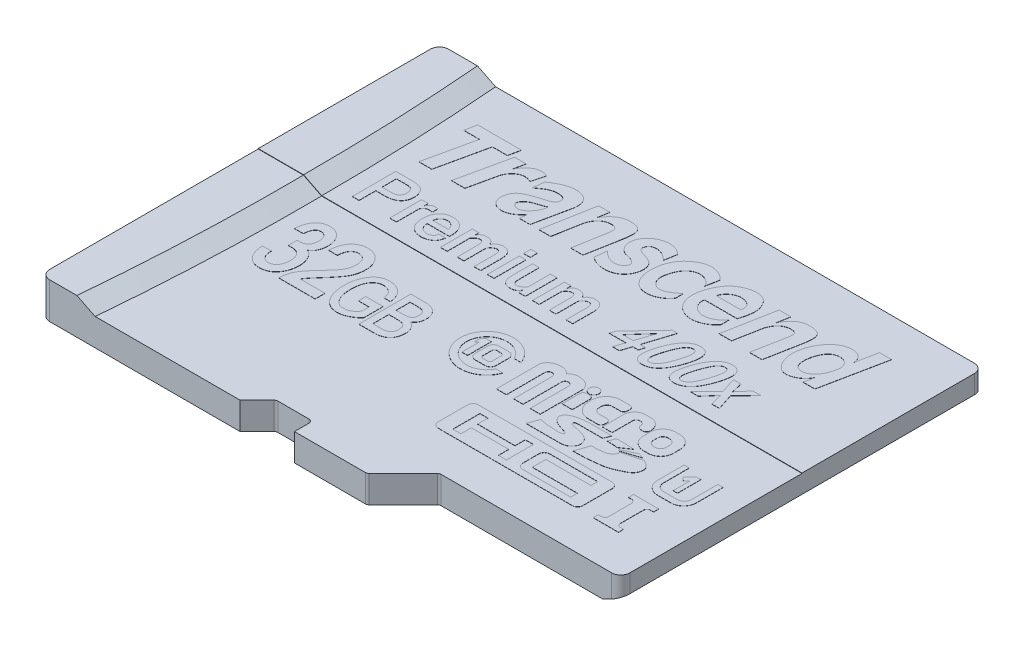
SolidWorks part; units mm, degrees
ref_plane "Front Plane" through (0, 0, 0) normal (0, 0, 1) x (1, 0, 0)
ref_plane "Top Plane" through (0, 0, 0) normal (0, 1, 0) x (1, 0, 0)
ref_plane "Right Plane" through (0, 0, 0) normal (1, 0, 0) x (0, 0, -1)
sketch "Sketch2" plane through (0, 0, 0) normal (0, 1, 0) x (1, 0, 0)
  line L0 (7.25, 5.5) -> (-7.25, 5.5)
  line L1 (-7.5, 5.25) -> (-7.5, -5.25)
  line L2 (-7.25, -5.5) -> (-2, -5.5)
  line L3 (-2, -5.5) -> (-1.5293, -5.0293)
  line L4 (-1.4586, -5) -> (-0.6, -5)
  line L5 (-0.5, -5.1) -> (-0.5, -5.5)
  line L8 (-0.5, -5.5) -> (1.4586, -5.5)
  line L9 (1.5293, -5.4707) -> (2.4707, -4.5293)
  line L10 (2.5414, -4.5) -> (7.25, -4.5)
  line L11 (7.5, -4.25) -> (7.5, 5.25)
  arc A0 (-1.4586, -5) -> (-1.5293, -5.0293) centre (-1.4586, -5.1) ccw
  arc A1 (-0.5, -5.1) -> (-0.6, -5) centre (-0.6, -5.1) ccw
  arc A3 (1.4586, -5.5) -> (1.5293, -5.4707) centre (1.4586, -5.4) ccw
  arc A4 (2.5414, -4.5) -> (2.4707, -4.5293) centre (2.5414, -4.6) ccw
  arc A5 (7.25, -4.5) -> (7.5, -4.25) centre (7.25, -4.25) ccw
  arc A6 (7.5, 5.25) -> (7.25, 5.5) centre (7.25, 5.25) ccw
  arc A7 (-7.5, -5.25) -> (-7.25, -5.5) centre (-7.25, -5.25) ccw
  arc A8 (-7.25, 5.5) -> (-7.5, 5.25) centre (-7.25, 5.25) ccw
  point P9 (-0.5, -5.5)
  point P10 (-0.5, -5.4707)
  point P26 (0, 0)
  point P28 (-7.5, -5.5)
  point P31 (-7.5, 5.5)
  dimension "D3" = 0.25
  dimension "D4" = 0.25
  dimension "D10" = 0.25
  dimension "D1" = 11
  dimension "D2" = 15
  dimension "D5" = 7.5
  dimension "D6" = 5.5
  dimension "D7" = 10
  dimension "D8" = 0.5
  dimension "D9" = 1
extrude "Boss-Extrude1" add sketch "Sketch2" along normal mid plane 1
sketch "Sketch4" plane through (0, 0, 0) normal (0, 0, 1) x (1, 0, 0)
  line L0 (-7.5, 0.5) -> (-6.25, 0.5)
  line L1 (-7.25, 0.5) -> (-2, 0.5) construction
  line L2 (-6.25, 0.5) -> (-5.75, 0.25)
  line L3 (-5.75, 0.25) -> (7.5, 0.25)
  line L4 (7.5, 0.5) -> (7.5, -0.5) construction
  line L5 (7.5, 0.25) -> (7.5, 1)
  line L6 (7.5, 1) -> (-7.5, 1)
  line L7 (-7.5, 1) -> (-7.5, 0.5)
  dimension "D1" = 0.75
  dimension "D2" = 0.75
  dimension "D3" = 1.25
  dimension "D4" = 0.5
extrude "Cut-Extrude1" cut sketch "Sketch4" against normal through all both and the other way through all
sketch "Sketch5" plane through (0, 0, 0) normal (0, 0, 1) x (1, 0, 0)
  line L1 (-4.75, 0.75) -> (-66.875, 0.75)
  line L2 (-66.875, 0.75) -> (-66.875, 0.5)
  line L4 (-7.5, 0.5) -> (-7.5, -0.5) construction
  line L5 (-66.875, 2.4541) -> (-66.875, -1.892) construction
  line L6 (-5.75, 0.25) -> (-6.25, 0.5)
  line L7 (-6.25, 0.5) -> (-66.875, 0.5)
  line L8 (-5.75, 0.25) -> (-4.75, 0.25)
  line L9 (-5.75, 0.25) -> (-2, 0.25) construction
  line L10 (-4.75, 0.25) -> (-4.75, 0.75)
  dimension "D1" = 0.5
  dimension "D2" = 59.375
  dimension "D3" = 1
revolve "Cut-Revolve1" cut sketch "Sketch5" angle 180 about L5 other way angle 0.5
ref_plane "Plane1" through (0, 0, -5.5) normal (0, 0, 1) x (1, 0, 0)
sketch "Sketch6" plane through (0, 0, -5.5) normal (0, 0, 1) x (1, 0, 0)
  line L0 (7.5, -0.5) -> (7.5, 0.26)
  line L2 (-7.5, 0.5) -> (-7.5, -0.5) construction
  line L4 (-7.5, -0.5) -> (-7.25, -0.5) construction
  line L5 (-7.5, -0.5) -> (7.5, -0.5)
  line L6 (-7.5, 0.51) -> (-5.5, 0.51)
  line L7 (-5.5, 0.51) -> (-5.5, 0.26)
  line L8 (-5.5, 0.26) -> (7.5, 0.26)
  line L9 (-7.5, 0.51) -> (-7.5, -0.5)
  dimension "D1" = 0.76
  dimension "D2" = 2
  dimension "D3" = 1.01
extrude "Boss-Extrude2" add sketch "Sketch6" along normal blind 5
ref_plane "Plane2" through (0, 0, -0.5) normal (0, 0, 1) x (1, 0, 0)
sketch "Sketch7" plane through (0, 0, -0.5) normal (0, 0, 1) x (1, 0, 0)
  line L0 (-6.2476, 0.51) -> (-5.7476, 0.26)
  line L2 (-6.2476, 0.51) -> (-67.5, 0.51)
  line L5 (7.5, 0.26) -> (-5.5, 0.26) construction
  line L6 (-5.75, 0.25) -> (-6.25, 0.5) construction
  line L7 (-5.7476, 0.26) -> (-5.2476, 0.26)
  line L8 (-5.2476, 0.26) -> (-5.2476, 0.76)
  line L9 (-5.2476, 0.76) -> (-67.5, 0.76)
  line L10 (-67.5, 0.76) -> (-67.5, 0.51)
  line L11 (-6.25, 0.5) -> (-6.5, 0.5) construction
  line L12 (-7.5, 0.5) -> (-7.5, -0.5) construction
  line L13 (-67.5, 1.5471) -> (-67.5, -0.1747) construction
  dimension "D1" = 0.01
  dimension "D2" = 0.01
  dimension "D3" = 0.5
  dimension "D4" = 0.5
  dimension "D5" = 60
revolve "Cut-Revolve2" cut sketch "Sketch7" angle 180 about L13 reverse direction yes
fillet "Fillet1" radius 0.25 2 edges at (-7.5, 0.005, -5.5) (7.5, -0.12, -5.5)
sketch "Sketch8" plane through (0, 0, 0) normal (0, 0, 1) x (1, 0, 0)
  line L0 (7.5, -0.25) -> (7, -0.5)
  line L1 (7.5, 0.25) -> (7.5, -0.5) construction
  line L2 (2.5414, -0.5) -> (7.25, -0.5) construction
  line L3 (7, -0.5) -> (7.5, -0.5)
  line L4 (7.5, -0.5) -> (7.5, -0.25)
  dimension "D1" = 0.25
  dimension "D2" = 0.5
extrude "Cut-Extrude2" cut sketch "Sketch8" against normal through all both and the other way through all
sketch "Sketch9" plane through (0, -0.5, 0) normal (0, -1, 0) x (1, 0, 0)
  line L0 (2.5414, 4.5) -> (7, 4.5) construction
  line L1 (6.5, 4) -> (3.5, 4)
  line L2 (6.5, 4) -> (6.5, 3.05)
  line L3 (6.5, 3.05) -> (3.5, 3.05)
  line L4 (3.5, 4) -> (3.5, 3.05)
  line L5 (6.5, 4) -> (3.5, 3.05) construction
  line L6 (6.5, 3.05) -> (3.5, 4) construction
  line L7 (6.5, 1.9) -> (3.5, 1.9)
  line L8 (6.5, 1.9) -> (6.5, 2.85)
  line L9 (6.5, 2.85) -> (3.5, 2.85)
  line L10 (3.5, 1.9) -> (3.5, 2.85)
  line L11 (6.5, 1.9) -> (3.5, 2.85) construction
  line L12 (6.5, 2.85) -> (3.5, 1.9) construction
  line L13 (6.5, 1.7) -> (3.5, 1.7)
  line L14 (6.5, 1.7) -> (6.5, 0.75)
  line L15 (6.5, 0.75) -> (3.5, 0.75)
  line L16 (3.5, 1.7) -> (3.5, 0.75)
  line L17 (6.5, 1.7) -> (3.5, 0.75) construction
  line L18 (6.5, 0.75) -> (3.5, 1.7) construction
  line L19 (6.5, -0.6) -> (3.5, -0.6)
  line L20 (6.5, -0.6) -> (6.5, -1.55)
  line L21 (6.5, -1.55) -> (3.5, -1.55)
  line L22 (3.5, -0.6) -> (3.5, -1.55)
  line L23 (6.5, -0.6) -> (3.5, -1.55) construction
  line L24 (6.5, -1.55) -> (3.5, -0.6) construction
  line L25 (6.75, -1.75) -> (3.5, -1.75)
  line L26 (6.75, -1.75) -> (6.75, -2.7)
  line L27 (6.75, -2.7) -> (3.5, -2.7)
  line L28 (3.5, -1.75) -> (3.5, -2.7)
  line L29 (6.75, -1.75) -> (3.5, -2.7) construction
  line L30 (6.75, -2.7) -> (3.5, -1.75) construction
  line L31 (3.5, -2.9) -> (6.5, -2.9)
  line L32 (3.5, -2.9) -> (3.5, -3.85)
  line L33 (3.5, -3.85) -> (6.5, -3.85)
  line L34 (6.5, -2.9) -> (6.5, -3.85)
  line L35 (3.5, -2.9) -> (6.5, -3.85) construction
  line L36 (3.5, -3.85) -> (6.5, -2.9) construction
  line L37 (6.5, -4.05) -> (3.5, -4.05)
  line L38 (6.5, -4.05) -> (6.5, -5)
  line L39 (6.5, -5) -> (3.5, -5)
  line L40 (3.5, -4.05) -> (3.5, -5)
  line L41 (6.5, -4.05) -> (3.5, -5) construction
  line L42 (6.5, -5) -> (3.5, -4.05) construction
  line L43 (6.75, 0.55) -> (3.5, 0.55)
  line L44 (6.75, 0.55) -> (6.75, -0.4)
  line L45 (6.75, -0.4) -> (3.5, -0.4)
  line L46 (3.5, 0.55) -> (3.5, -0.4)
  line L47 (6.75, 0.55) -> (3.5, -0.4) construction
  line L48 (6.75, -0.4) -> (3.5, 0.55) construction
  line L51 (7.5, -5.25) -> (7.5, 4.25) construction
  point P0 (5, 3.525)
  point P5 (5, 2.375)
  point P10 (5, 1.225)
  point P15 (5, -1.075)
  point P20 (5.125, -2.225)
  point P25 (5, -3.375)
  point P30 (5, -4.525)
  point P35 (5.125, 0.075)
  dimension "D1" = 0.95
  dimension "D2" = 0.2
  dimension "D3" = 0.2
  dimension "D4" = 0.2
  dimension "D5" = 0.2
  dimension "D6" = 0.2
  dimension "D7" = 0.2
  dimension "D8" = 0.2
  dimension "D9" = 0.5
  dimension "D10" = 4
  dimension "D11" = 3
  dimension "D12" = 3.25
extrude "Boss-Extrude3" add sketch "Sketch9" along normal blind 0.01
sketch "Sketch10" plane through (0, -0.5, 0) normal (0, -1, 0) x (1, 0, 0)
  line L0 (-1.4611, 4.2914) -> (-1.4611, -4.3118) construction
  line L1 (-7.5, -5.25) -> (-7.5, 5.25) construction
  text T0 "  C84931 4707" font "Microsoft Sans Serif" height in points 4
  point P4 (-1.4611, -4.9453)
  point P5 (-1.4611, 4.2914)
  point P6 (-1.502, -4.1074)
  point P8 (0, 0)
  point P9 (-1.4611, -4.3118)
  dimension "D1" = 6.0389
extrude "Boss-Extrude4" add sketch "Sketch10" along normal blind 0.01
sketch "Sketch11" plane through (0, -0.5, 0) normal (0, -1, 0) x (1, 0, 0)
  line L0 (-5.5, 4.7) -> (-5.5, -4.8286) construction
  line L1 (-7.5, -5.25) -> (-7.5, 5.25) construction
  line L3 (-7.25, 5.5) -> (-2, 5.5) construction
  text T0 "9181AA  32G  01DS2" font "Microsoft Sans Serif" height in points 3
  point P5 (-5.5, -4.8286)
  point P6 (-5.5, 4.6961)
  dimension "D1" = 2
  dimension "D2" = 0.8
extrude "Boss-Extrude5" add sketch "Sketch11" along normal blind 0.005
sketch "Sketch13" plane through (0, -0.5, 0) normal (0, -1, 0) x (1, 0, 0)
  line L0 (-6.75, 4.7) -> (-6.75, -4.9658) construction
  line L1 (-7.25, 5.5) -> (-2, 5.5) construction
  line L3 (-7.5, -5.25) -> (-7.5, 5.25) construction
  text T0 "Made  In  Taiwan" font "Microsoft Sans Serif" height in points 3
  dimension "D1" = 0.8
  dimension "D2" = 0.75
extrude "Boss-Extrude6" add sketch "Sketch13" along normal blind 0.005
sketch "Sketch15" plane through (0, 0.26, 0) normal (0, 1, 0) x (1, 0, 0)
  line L0 (158.8303, 491.6959) -> (825.497, 491.6959) construction
  line L1 (-5.2862, 4.338) -> (-5.3422, 4.0172)
  line L2 (-5.3422, 4.0172) -> (-4.9144, 4.0172)
  line L3 (-4.9144, 4.0172) -> (-5.2149, 2.6473)
  line L4 (-5.2149, 2.6473) -> (-4.8584, 2.6473)
  line L5 (-4.8584, 2.6473) -> (-4.5579, 4.0172)
  line L6 (-4.5579, 4.0172) -> (-4.1455, 4.0172)
  line L7 (-4.1455, 4.0172) -> (-4.0751, 4.338)
  line L8 (-4.0751, 4.338) -> (-5.2862, 4.338)
  line L9 (-4.0029, 4.0732) -> (-4.3156, 2.6473)
  line L10 (-4.3156, 2.6473) -> (-3.9474, 2.6473)
  line L11 (-3.9474, 2.6473) -> (-3.7739, 3.4383)
  line L12 (-4.0029, 4.0732) -> (-3.6821, 4.0732)
  line L13 (-3.6821, 4.0732) -> (-3.7527, 3.7511)
  line L14 (-3.1168, 4.0732) -> (-3.2136, 3.7014)
  line L15 (-2.9924, 3.8987) -> (-3.0268, 3.5897)
  line L16 (-2.4525, 2.8946) -> (-2.48, 2.6814)
  line L17 (-2.48, 2.6814) -> (-2.1843, 2.6814)
  line L18 (-2.1843, 2.6814) -> (-1.9711, 3.7014)
  line L21 (-1.9361, 2.6814) -> (-1.6843, 4.0732)
  line L22 (-1.6843, 4.0732) -> (-1.3721, 4.0732)
  line L23 (-1.3721, 4.0732) -> (-1.4304, 3.7511)
  line L24 (-1.9361, 2.6814) -> (-1.6138, 2.6814)
  line L25 (-1.6138, 2.6814) -> (-1.4715, 3.468)
  line L26 (-0.8988, 3.5897) -> (-1.0631, 2.6814)
  line L27 (-1.0631, 2.6814) -> (-0.7243, 2.6814)
  line L28 (-0.7243, 2.6814) -> (-0.5397, 3.7014)
  line L29 (0.5669, 3.9963) -> (0.5114, 3.662)
  line L30 (-0.4808, 3.1215) -> (-0.52, 2.7788)
  line L31 (1.7649, 3.9712) -> (1.6987, 3.6155)
  line L32 (1.5815, 3.1416) -> (1.5815, 2.9253)
  line L33 (2.0827, 3.5483) -> (2.7624, 3.5483)
  line L34 (2.0249, 3.288) -> (2.9251, 3.288)
  line L35 (2.8419, 3.1416) -> (2.8419, 2.9253)
  line L36 (3.0337, 2.6814) -> (3.2951, 4.0714)
  line L37 (3.2951, 4.0714) -> (3.6224, 4.0714)
  line L38 (3.6224, 4.0714) -> (3.5565, 3.7213)
  line L39 (3.0337, 2.6814) -> (3.3731, 2.6814)
  line L40 (3.3731, 2.6814) -> (3.5154, 3.4382)
  line L41 (4.0687, 3.5636) -> (3.8974, 2.6528)
  line L42 (3.8974, 2.6528) -> (4.2442, 2.6528)
  line L43 (4.2442, 2.6528) -> (4.4362, 3.6737)
  line L44 (5.6976, 4.4384) -> (6.0299, 4.4384)
  line L45 (6.0299, 4.4384) -> (5.6739, 2.6814)
  line L46 (5.6739, 2.6814) -> (5.3484, 2.6814)
  line L47 (5.3484, 2.6814) -> (5.4066, 2.9686)
  line L48 (5.6976, 4.4384) -> (5.5783, 3.8494)
  line L49 (-2.359, 3.2688) -> (-2.3486, 3.354)
  spline S0 degree 3 poles (-3.7527, 3.7511) (-3.6407, 3.9755) (-3.4147, 4.1987) (-3.1168, 4.0732) knots 0 0 0 0 1 1 1 1
  spline S1 degree 3 poles (-3.7739, 3.4383) (-3.707, 3.6572) (-3.469, 3.854) (-3.2136, 3.7014) knots 0 0 0 0 1 1 1 1
  spline S2 degree 3 poles (-2.9924, 3.8987) (-2.8373, 4.0051) (-2.4473, 4.234) (-1.9267, 4.089) (-1.9711, 3.7014) knots 0 0 0 0 0.427464 1 1 1 1
  spline S3 degree 3 poles (-3.0268, 3.5897) (-2.9262, 3.6662) (-2.7469, 3.8047) (-2.4945, 3.8221) (-2.3204, 3.7633) (-2.3195, 3.5384) (-2.6092, 3.4705) (-2.8655, 3.3808) (-3.1477, 3.263) (-3.2689, 2.9868) (-3.1997, 2.6846) (-2.8048, 2.5588) (-2.5561, 2.7501) (-2.4525, 2.8946) knots 0 0 0 0 0.125339 0.201806 0.242081 0.279775 0.378143 0.472332 0.560271 0.655256 0.737774 0.82471 1 1 1 1
  spline S4 degree 3 poles (-2.3486, 3.354) (-2.5064, 3.2611) (-2.7369, 3.2767) (-2.9384, 2.9914) (-2.6347, 2.7517) (-2.3775, 3.1441) (-2.359, 3.2688) knots 0 0 0 0 0.359916 0.478899 0.575608 1 1 1 1
  spline S5 degree 3 poles (-1.4304, 3.7511) (-1.3229, 3.9458) (-1.0782, 4.186) (-0.5312, 4.103) (-0.5169, 3.9068) (-0.5397, 3.7014) knots 0 0 0 0 0.477961 0.720245 1 1 1 1
  spline S6 degree 3 poles (-1.4715, 3.468) (-1.4275, 3.6194) (-1.2734, 3.8305) (-0.9177, 3.8046) (-0.8856, 3.7054) (-0.8988, 3.5897) knots 0 0 0 0 0.54471 0.774016 1 1 1 1
  spline S7 degree 3 poles (0.5669, 3.9963) (0.4245, 4.1604) (0.0713, 4.1878) (-0.3085, 3.9466) (-0.45, 3.5885) (-0.2437, 3.2852) (-0.0068, 3.2776) (0.2118, 3.1384) (-0.0449, 2.8001) (-0.3756, 2.9847) (-0.4808, 3.1215) knots 0 0 0 0 0.21526 0.330731 0.465297 0.578093 0.652065 0.72378 0.787706 1 1 1 1
  spline S8 degree 3 poles (-0.52, 2.7788) (-0.3271, 2.6259) (0.1314, 2.5732) (0.4603, 2.9649) (0.484, 3.3777) (0.1857, 3.5186) (-0.1102, 3.583) (-0.0426, 3.8241) (0.2373, 3.885) (0.4177, 3.7609) (0.5114, 3.662) knots 0 0 0 0 0.273899 0.389369 0.52759 0.637897 0.730225 0.781048 0.851979 1 1 1 1
  spline S9 degree 3 poles (1.6987, 3.6155) (1.6353, 3.7933) (1.2773, 3.925) (0.9827, 3.6447) (0.8803, 3.3712) (0.8613, 3.0739) (1.1849, 2.8102) (1.4705, 3.0525) (1.5815, 3.1416) knots 0 0 0 0 0.249144 0.382676 0.50918 0.650083 0.751503 1 1 1 1
  spline S10 degree 3 poles (1.5815, 2.9253) (1.4692, 2.7716) (1.1993, 2.6072) (0.7921, 2.6749) (0.579, 2.9508) (0.5474, 3.3325) (0.6378, 3.7423) (0.9132, 4.0416) (1.3205, 4.2365) (1.6462, 4.1211) (1.7649, 3.9712) knots 0 0 0 0 0.175141 0.260201 0.354064 0.468722 0.602099 0.725908 0.827802 1 1 1 1
  spline S11 degree 3 poles (2.9251, 3.288) (2.9845, 3.4777) (3.0667, 3.8058) (2.7712, 4.2244) (2.3523, 4.1734) (1.9835, 3.9584) (1.7665, 3.5529) (1.701, 3.0955) (1.9113, 2.7446) (2.3511, 2.5665) (2.7078, 2.7438) (2.8419, 2.9253) knots 0 0 0 0 0.153735 0.227091 0.34284 0.421144 0.543478 0.670248 0.746283 0.830069 1 1 1 1
  spline S12 degree 3 poles (2.0249, 3.288) (1.9797, 3.0931) (2.3276, 2.7379) (2.7286, 2.9979) (2.8419, 3.1416) knots 0 0 0 0 0.473851 1 1 1 1
  spline S13 degree 3 poles (2.0827, 3.5483) (2.1348, 3.7177) (2.4404, 3.9586) (2.8155, 3.7601) (2.7624, 3.5483) knots 0 0 0 0 0.518429 1 1 1 1
  spline S14 degree 3 poles (3.5565, 3.7213) (3.6506, 3.9205) (3.8841, 4.173) (4.4549, 4.0813) (4.4586, 3.8752) (4.4362, 3.6737) knots 0 0 0 0 0.455916 0.725539 1 1 1 1
  spline S15 degree 3 poles (3.5154, 3.4382) (3.5628, 3.5902) (3.7063, 3.7994) (4.0752, 3.7768) (4.0815, 3.6758) (4.0687, 3.5636) knots 0 0 0 0 0.549476 0.780788 1 1 1 1
  spline S16 degree 3 poles (5.5783, 3.8494) (5.5592, 4.1376) (5.1279, 4.2091) (4.7223, 3.8887) (4.5013, 3.4516) (4.4939, 2.9566) (4.8844, 2.4839) (5.3323, 2.7662) (5.4066, 2.9686) knots 0 0 0 0 0.207472 0.326046 0.481805 0.666148 0.774125 1 1 1 1
  spline S17 degree 3 poles (5.4203, 3.1268) (5.5117, 3.3885) (5.5486, 3.6091) (5.3809, 3.8102) (5.0554, 3.7984) (4.8954, 3.5148) (4.8358, 3.2482) (4.8567, 2.9415) (5.216, 2.8879) (5.4203, 3.1268) (5.5117, 3.3885) (5.5486, 3.6091) knots -0.338143 -0.248717 -0.08126 0 0.107798 0.173296 0.302086 0.439095 0.539418 0.661857 0.751283 0.91874 1 1.107798 1.173296 1.302086 only from (5.501, 3.3736) to (5.501, 3.3736)
  point P157 (-2.3408, 3.7437)
  point P161 (-2.333, 3.626)
extrude "Boss-Extrude7" add sketch "Sketch15" along normal blind 0.005
sketch "Sketch17" plane through (0, 0.26, 0) normal (0, 1, 0) x (1, 0, 0)
  line L0 (-5.4255, 0.9) -> (0.8836, 0.9) construction
  line L1 (7.5, 0.5) -> (-5.7476, 0.5) construction
  text T0 "Premium" font "Microsoft Sans Serif" height 1.2
  point P5 (-5.5165, 0.9)
  point P6 (-5.4255, 0.9)
  dimension "D1" = 0.4
extrude "Boss-Extrude8" add sketch "Sketch17" along normal blind 0.005
sketch "Sketch18" plane through (0, 0.26, 0) normal (0, 1, 0) x (1, 0, 0)
  line L0 (1.3851, 0.9) -> (5.1819, 0.9) construction
  line L1 (7.5, 0.5) -> (-5.7476, 0.5) construction
  text T0 "400x" font "Microsoft Sans Serif" height 1.2
  dimension "D1" = 0.4
extrude "Boss-Extrude9" add sketch "Sketch18" along normal blind 0.005
sketch "Sketch19" plane through (0, 0.25, 0) normal (0, 1, 0) x (1, 0, 0)
  line L0 (-5.4698, -2.05) -> (-1.0866, -2.05) construction
  line L1 (-5.9979, -5.5) -> (-2, -5.5) construction
  text T0 "32" font "Microsoft Sans Serif" height in points 8
  dimension "D1" = 3.45
extrude "Boss-Extrude10" add sketch "Sketch19" along normal blind 0.005
sketch "Sketch20" plane through (0, 0.25, 0) normal (0, 1, 0) x (1, 0, 0)
  line L0 (-3.774, -2.05) -> (-0.8585, -2.05) construction
  line L1 (-3.3771, -2.05) -> (-4.3818, -2.05) construction
  line L2 (-3.3771, -2.05) -> (-4.3818, -2.05) construction
  text T0 "GB" font "Microsoft Sans Serif" height in points 6
  point P6 (-0.8585, -2.05)
  point P7 (-3.3771, -2.05)
  point P10 (-3.5784, -2.05)
  point P11 (-3.774, -2.05)
extrude "Boss-Extrude11" add sketch "Sketch20" along normal blind 0.005
sketch "Sketch21" plane through (0, 0.255, 0) normal (0, 1, 0) x (1, 0, 0)
  line L0 (-2.259, -1.2965) -> (-2.259, -2.05) construction
  line L1 (-2.259, -1.2965) -> (-2.259, -2.05) construction
  line L2 (-2.259, -1.8294) -> (-2.259, -1.6982)
  line L3 (-2.259, -1.6982) -> (-2.622, -1.9356)
  line L4 (-2.622, -1.9356) -> (-2.5746, -2.0367)
  spline S0 degree 2 poles (-2.5746, -2.0367) (-2.3903, -1.9703) (-2.259, -1.8294) knots 0 0 0 1 1 1
  spline S2 degree 3 poles (-2.4284, -1.9035) (-2.4355, -1.9168) (-2.4495, -1.9429) (-2.4789, -1.9765) (-2.513, -2.0054) (-2.5532, -2.0285) (-2.5987, -2.0466) (-2.6499, -2.0593) (-2.7066, -2.0671) (-2.7463, -2.0679) (-2.767, -2.0684) knots 0 0 0 0 0.112738 0.222655 0.333672 0.448018 0.569947 0.70158 0.844182 1 1 1 1 construction
extrude "Boss-Extrude12" add sketch "Sketch21" against normal blind 0.005
sketch "Sketch22" plane through (0, 0.25, 0) normal (0, 1, 0) x (1, 0, 0)
  line L0 (-2.259, -1.8294) -> (-2.259, -2.0681)
  line L1 (-2.259, -2.0681) -> (-2.5746, -2.0681)
  line L2 (-2.5746, -2.0681) -> (-2.5746, -2.0367)
  parabola Q0 (-2.5746, -2.0367) -> (-2.259, -1.8294) focus (-2.6055, -1.6185) apex (-2.3801, -1.9356) construction
  parabola Q1 (-2.5746, -2.0367) -> (-2.259, -1.8294) focus (-2.6055, -1.6185) apex (-2.3801, -1.9356)
extrude "Cut-Extrude4" cut sketch "Sketch22" along normal blind 0.005
sketch "Sketch23" plane through (0, 0.25, 0) normal (0, 1, 0) x (1, 0, 0)
  line L0 (0.787, -0.7291) -> (0.9803, -0.7291)
  line L1 (0.787, -1.2312) -> (0.9803, -1.2312)
  line L2 (-0.0838, -1.2966) -> (0.0714, -1.2966)
  line L3 (0.0714, -1.2966) -> (0.0714, -0.641)
  line L4 (0.0714, -0.641) -> (-0.0838, -0.641)
  line L5 (-0.0838, -0.641) -> (-0.1581, -0.7152)
  line L6 (-0.1581, -0.7152) -> (-0.1581, -0.8857)
  line L7 (-0.1581, -0.8857) -> (-0.0838, -0.8114)
  line L8 (-0.0838, -0.8114) -> (-0.0838, -1.2966)
  line L9 (1.2708, -1.6991) -> (1.5458, -1.6991)
  line L10 (0.3492, -0.7776) -> (0.4882, -0.7776)
  line L11 (0.2892, -0.8376) -> (0.2892, -1.0992)
  line L12 (0.3492, -1.1592) -> (0.4882, -1.1592)
  line L13 (0.5482, -0.8376) -> (0.5482, -1.0992)
  line L14 (0.2892, -0.7776) -> (0.5482, -1.1592) construction
  line L15 (0.2892, -1.1592) -> (0.5482, -0.7776) construction
  line L16 (0.2799, -0.6402) -> (0.5575, -0.6402)
  line L17 (0.1299, -0.7902) -> (0.1299, -1.1466)
  line L18 (0.2799, -1.2966) -> (0.5575, -1.2966)
  line L19 (0.7075, -0.7902) -> (0.7075, -1.1466)
  line L20 (0.1299, -0.6402) -> (0.7075, -1.2966) construction
  line L21 (0.1299, -1.2966) -> (0.7075, -0.6402) construction
  line L22 (1.5458, -1.6991) -> (1.5458, -0.6402)
  line L23 (1.2708, -1.6991) -> (1.2708, -0.5012)
  line L24 (1.8741, -0.2054) -> (1.8741, -1.7553) construction
  line L25 (1.7436, -1.6991) -> (1.7436, -0.6402)
  line L26 (2.0045, -1.6991) -> (2.0045, -0.6402)
  line L27 (2.4774, -1.6991) -> (2.4774, -0.5012)
  line L28 (2.2023, -1.6991) -> (2.2023, -0.6402)
  line L29 (2.4774, -1.6991) -> (2.2023, -1.6991)
  line L30 (1.7436, -1.6991) -> (2.0045, -1.6991)
  line L31 (2.5303, -1.1466) -> (2.8095, -1.1466)
  line L32 (2.5303, -1.1466) -> (2.5303, -0.6637)
  line L33 (2.6303, -0.5637) -> (2.7095, -0.5637)
  line L34 (2.8095, -0.6637) -> (2.8095, -1.1466)
  line L35 (3.6027, -0.9857) -> (3.6027, -1.0466)
  line L36 (3.2863, -0.5185) -> (3.5027, -0.5185)
  line L37 (3.1363, -0.6685) -> (3.1363, -0.7357)
  line L38 (3.2863, -0.8857) -> (3.5027, -0.8857)
  line L40 (3.1363, -0.5185) -> (3.6027, -0.8857) construction
  line L41 (3.1363, -0.8857) -> (3.6027, -0.5185) construction
  line L42 (3.2499, -0.2504) -> (3.5027, -0.2504)
  line L43 (2.8499, -0.6504) -> (2.8499, -0.7466)
  line L44 (3.2499, -1.1466) -> (3.5027, -1.1466)
  line L45 (3.6027, -0.3504) -> (3.6027, -0.4185)
  line L46 (2.8499, -0.2504) -> (3.6027, -1.1466) construction
  line L47 (2.8499, -1.1466) -> (3.6027, -0.2504) construction
  line L48 (3.6375, -0.5614) -> (3.6375, -1.1466)
  line L49 (3.6375, -1.1466) -> (3.9091, -1.1466)
  line L50 (3.9091, -1.1466) -> (3.9091, -0.583)
  line L51 (3.9375, -0.2614) -> (4.0935, -0.2614)
  line L52 (4.3934, -0.5685) -> (4.393, -0.5863)
  line L53 (4.293, -0.684) -> (4.2369, -0.684)
  line L54 (4.1369, -0.584) -> (4.1369, -0.583)
  line L55 (4.0369, -0.483) -> (4.0091, -0.483)
  line L56 (3.9874, -1.2312) -> (3.9114, -1.4138)
  line L57 (4.8124, -0.5012) -> (4.8584, -0.5012)
  line L58 (4.6624, -0.6512) -> (4.6624, -0.7576)
  line L59 (4.8124, -0.9076) -> (4.8584, -0.9076)
  line L60 (5.0084, -0.6512) -> (5.0084, -0.7576)
  line L61 (4.6624, -0.5012) -> (5.0084, -0.9076) construction
  line L62 (4.6624, -0.9076) -> (5.0084, -0.5012) construction
  line L63 (4.772, -0.2621) -> (4.8988, -0.2621)
  line L64 (4.422, -0.6121) -> (4.422, -0.7966)
  line L65 (4.772, -1.1466) -> (4.8988, -1.1466)
  line L66 (5.2488, -0.6121) -> (5.2488, -0.7966)
  line L67 (4.422, -0.2621) -> (5.2488, -1.1466) construction
  line L68 (4.422, -1.1466) -> (5.2488, -0.2621) construction
  line L69 (2.505, -2.1156) -> (2.6129, -1.8203)
  line L70 (2.505, -2.1156) -> (3.4415, -2.1156)
  line L71 (3.9114, -1.4138) -> (3.2148, -1.4138)
  line L72 (3.9874, -1.2312) -> (3.4062, -1.2312)
  line L73 (4.122, -1.2312) -> (4.0444, -1.4177)
  line L74 (3.9375, -1.7553) -> (3.8087, -2.1274)
  line L75 (4.4769, -1.5186) -> (5.018, -1.3725)
  line L76 (4.4497, -1.4902) -> (4.9316, -1.332)
  line L77 (4.4067, -1.462) -> (4.7897, -1.2837)
  line L78 (4.3329, -1.4362) -> (4.6022, -1.2496)
  line L79 (6.6072, -0.9287) -> (6.75, -0.9287)
  line L80 (5.6764, -0.9287) -> (5.8194, -0.9287)
  line L81 (5.6764, -0.9287) -> (5.6764, -1.6659)
  line L82 (6.0264, -2.0159) -> (6.4, -2.0159)
  line L83 (6.75, -0.9287) -> (6.75, -1.6659)
  line L84 (5.6764, -0.9287) -> (6.75, -2.0159) construction
  line L85 (5.6764, -2.0159) -> (6.75, -0.9287) construction
  line L86 (6.0194, -1.8497) -> (6.4072, -1.8497)
  line L87 (5.8194, -1.6497) -> (5.8194, -0.9287)
  line L89 (6.6072, -1.6497) -> (6.6072, -0.9287)
  line L90 (5.8194, -1.8497) -> (6.6072, -0.9287) construction
  line L91 (5.8194, -0.9287) -> (6.6072, -1.8497) construction
  line L92 (6.035, -1.3242) -> (5.9483, -1.2364)
  line L93 (5.9483, -1.2364) -> (6.1405, -1.0466)
  line L94 (6.1405, -1.0466) -> (6.2572, -1.0466)
  line L95 (6.2572, -1.0466) -> (6.2572, -1.6912)
  line L96 (6.2572, -1.6912) -> (6.1387, -1.6912)
  line L97 (6.1387, -1.6912) -> (6.1387, -1.2292)
  line L98 (6.1387, -1.2292) -> (6.035, -1.3242)
  line L99 (5.1746, -3.4199) -> (5.2488, -3.4405) construction
  line L100 (1.4043, -2.3311) -> (5.0988, -2.3311)
  line L101 (1.2543, -2.4811) -> (1.2543, -3.2905)
  line L102 (1.4043, -3.4405) -> (5.0988, -3.4405)
  line L103 (5.2488, -2.4811) -> (5.2488, -3.2905)
  line L104 (1.2543, -2.3311) -> (1.3284, -2.3517) construction
  line L105 (1.2543, -3.4405) -> (1.3284, -3.4199) construction
  line L106 (5.1746, -2.3517) -> (5.2488, -2.3311) construction
  line L107 (1.6307, -2.5164) -> (1.8534, -2.5164)
  line L108 (1.8534, -2.5164) -> (1.8534, -2.8001)
  line L109 (1.8534, -2.8001) -> (2.8839, -2.8001)
  line L110 (2.8839, -2.8001) -> (2.8839, -2.5164)
  line L111 (2.8839, -2.5164) -> (3.1067, -2.5164)
  line L112 (3.1067, -2.5164) -> (3.1067, -3.2614)
  line L113 (3.1067, -3.2614) -> (2.8839, -3.2614)
  line L114 (2.8839, -3.2614) -> (2.8839, -2.9738)
  line L115 (2.8839, -2.9738) -> (1.8534, -2.9738)
  line L116 (1.8534, -2.9738) -> (1.8534, -3.2614)
  line L117 (1.8534, -3.2614) -> (1.6307, -3.2614)
  line L118 (1.6307, -3.2614) -> (1.6307, -2.5164)
  line L119 (4.8823, -2.5164) -> (4.8823, -2.7029)
  line L120 (4.8823, -2.7029) -> (3.6375, -2.7029)
  line L121 (3.6375, -2.7029) -> (3.6375, -3.0748)
  line L122 (3.6375, -3.0748) -> (4.8823, -3.0748)
  line L123 (4.8823, -3.0748) -> (4.8823, -3.2614)
  line L124 (4.8823, -3.2614) -> (3.5562, -3.2614)
  line L125 (3.4062, -3.1114) -> (3.4062, -2.6664)
  line L126 (3.5562, -2.5164) -> (4.8823, -2.5164)
  line L127 (5.6838, -2.4709) -> (5.8684, -2.4709)
  line L129 (5.6838, -2.4709) -> (5.6838, -2.3311)
  line L130 (5.6838, -2.3311) -> (6.3775, -2.3311)
  line L131 (6.3775, -2.4709) -> (6.3775, -2.3311)
  line L132 (5.6838, -3.4405) -> (6.3775, -2.3311) construction
  line L133 (5.6838, -2.3311) -> (6.3775, -3.4405) construction
  line L134 (5.8684, -2.4709) -> (5.8684, -3.3007)
  line L135 (6.3775, -2.4709) -> (6.1929, -2.4709)
  line L136 (6.1929, -2.4709) -> (6.1929, -3.3007)
  line L137 (5.9483, -2.8858) -> (6.1245, -2.8858) construction
  line L138 (5.6838, -3.3007) -> (5.8684, -3.3007)
  line L139 (5.6838, -3.3007) -> (5.6838, -3.4405)
  line L140 (5.6838, -3.4405) -> (6.3775, -3.4405)
  line L141 (6.3775, -3.3007) -> (6.3775, -3.4405)
  line L142 (6.3775, -3.3007) -> (6.1929, -3.3007)
  arc A0 (0.9803, -0.7291) -> (0.9803, -1.2312) centre (0.2866, -0.9801) ccw
  arc A1 (0.787, -0.7291) -> (0.787, -1.2312) centre (0.2866, -0.9801) ccw
  arc A2 (0.4882, -1.1592) -> (0.5482, -1.0992) centre (0.4882, -1.0992) ccw
  arc A3 (0.2892, -1.0992) -> (0.3492, -1.1592) centre (0.3492, -1.0992) ccw
  arc A4 (0.3492, -0.7776) -> (0.2892, -0.8376) centre (0.3492, -0.8376) ccw
  arc A5 (0.4882, -0.7776) -> (0.5482, -0.8376) centre (0.4882, -0.8376) cw
  arc A6 (0.5575, -1.2966) -> (0.7075, -1.1466) centre (0.5575, -1.1466) ccw
  arc A7 (0.1299, -1.1466) -> (0.2799, -1.2966) centre (0.2799, -1.1466) ccw
  arc A8 (0.2799, -0.6402) -> (0.1299, -0.7902) centre (0.2799, -0.7902) ccw
  arc A9 (0.5575, -0.6402) -> (0.7075, -0.7902) centre (0.5575, -0.7902) cw
  arc A11 (1.7436, -0.6402) -> (1.5458, -0.6402) centre (1.6447, -0.6402) ccw
  arc A12 (2.0045, -0.6402) -> (2.2023, -0.6402) centre (2.1034, -0.6402) cw
  circle A13 centre (2.6659, -0.4029) radius 0.135
  arc A15 (2.5303, -0.6637) -> (2.6303, -0.5637) centre (2.6303, -0.6637) cw
  arc A16 (2.8095, -0.6637) -> (2.7095, -0.5637) centre (2.7095, -0.6637) ccw
  arc A17 (3.5027, -1.1466) -> (3.6027, -1.0466) centre (3.5027, -1.0466) ccw
  arc A18 (3.5027, -0.8857) -> (3.6027, -0.9857) centre (3.5027, -0.9857) cw
  arc A19 (3.5027, -0.5185) -> (3.6027, -0.4185) centre (3.5027, -0.4185) ccw
  arc A20 (3.5027, -0.2504) -> (3.6027, -0.3504) centre (3.5027, -0.3504) cw
  arc A21 (3.2863, -0.5185) -> (3.1363, -0.6685) centre (3.2863, -0.6685) ccw
  arc A22 (3.1363, -0.7357) -> (3.2863, -0.8857) centre (3.2863, -0.7357) ccw
  arc A23 (2.8499, -0.7466) -> (3.2499, -1.1466) centre (3.2499, -0.7466) ccw
  arc A24 (3.2499, -0.2504) -> (2.8499, -0.6504) centre (3.2499, -0.6504) ccw
  arc A25 (4.1369, -0.583) -> (4.0369, -0.483) centre (4.0369, -0.583) ccw
  arc A26 (3.9091, -0.583) -> (4.0091, -0.483) centre (4.0091, -0.583) cw
  arc A27 (4.393, -0.5863) -> (4.293, -0.684) centre (4.293, -0.584) cw
  arc A28 (4.1369, -0.584) -> (4.2369, -0.684) centre (4.2369, -0.584) ccw
  arc A29 (4.0935, -0.2614) -> (4.3934, -0.5685) centre (4.0935, -0.5614) cw
  arc A30 (3.6375, -0.5614) -> (3.9375, -0.2614) centre (3.9375, -0.5614) cw
  arc A31 (4.8988, -1.1466) -> (5.2488, -0.7966) centre (4.8988, -0.7966) ccw
  arc A32 (4.422, -0.7966) -> (4.772, -1.1466) centre (4.772, -0.7966) ccw
  arc A33 (4.772, -0.2621) -> (4.422, -0.6121) centre (4.772, -0.6121) ccw
  arc A34 (4.8988, -0.2621) -> (5.2488, -0.6121) centre (4.8988, -0.6121) cw
  arc A35 (4.8584, -0.9076) -> (5.0084, -0.7576) centre (4.8584, -0.7576) ccw
  arc A36 (4.6624, -0.7576) -> (4.8124, -0.9076) centre (4.8124, -0.7576) ccw
  arc A37 (4.8124, -0.5012) -> (4.6624, -0.6512) centre (4.8124, -0.6512) ccw
  arc A38 (4.8584, -0.5012) -> (5.0084, -0.6512) centre (4.8584, -0.6512) cw
  arc A39 (6.4072, -1.8497) -> (6.6072, -1.6497) centre (6.4072, -1.6497) ccw
  arc A40 (6.0194, -1.8497) -> (5.8194, -1.6497) centre (6.0194, -1.6497) cw
  arc A41 (6.4, -2.0159) -> (6.75, -1.6659) centre (6.4, -1.6659) ccw
  arc A42 (5.6764, -1.6659) -> (6.0264, -2.0159) centre (6.0264, -1.6659) ccw
  arc A43 (5.0988, -2.3311) -> (5.2488, -2.4811) centre (5.0988, -2.4811) cw
  arc A44 (5.0988, -3.4405) -> (5.2488, -3.2905) centre (5.0988, -3.2905) ccw
  arc A45 (1.2543, -3.2905) -> (1.4043, -3.4405) centre (1.4043, -3.2905) ccw
  arc A46 (1.4043, -2.3311) -> (1.2543, -2.4811) centre (1.4043, -2.4811) ccw
  arc A47 (3.5562, -3.2614) -> (3.4062, -3.1114) centre (3.5562, -3.1114) cw
  arc A48 (3.4062, -2.6664) -> (3.5562, -2.5164) centre (3.5562, -2.6664) cw
  spline S0 degree 3 poles (1.2708, -0.5012) (1.3183, -0.3422) (1.5703, -0.2192) (1.8139, -0.2994) (1.8741, -0.3751) knots 0 0 0 0 0.620045 1 1 1 1
  spline S1 degree 3 poles (2.4774, -0.5012) (2.4298, -0.3422) (2.1778, -0.2192) (1.9343, -0.2994) (1.8741, -0.3751) knots 0 0 0 0 0.620045 1 1 1 1
  spline S2 degree 3 poles (3.2148, -1.4138) (3.1874, -1.415) (3.1486, -1.4186) (3.124, -1.4921) (3.2116, -1.518) (3.3199, -1.5374) (3.4876, -1.5769) (3.6919, -1.6522) (3.7894, -1.8821) (3.6498, -2.0829) (3.5203, -2.1127) (3.4415, -2.1156) knots 0.079407 0.079407 0.079407 0.079407 0.12655 0.149302 0.210494 0.265859 0.401127 0.563952 0.704929 0.857186 1 1 1 1
  spline S3 degree 3 poles (3.4062, -1.2312) (3.2916, -1.2331) (3.1138, -1.2478) (2.8979, -1.3199) (2.7462, -1.4715) (2.8822, -1.6745) (3.0658, -1.7249) (3.1963, -1.771) (3.2734, -1.7943) (3.2853, -1.8411) (3.196, -1.8789) (2.9873, -1.8697) (2.7593, -1.8545) (2.6129, -1.8203) knots 0 0 0 0 0.166933 0.264176 0.343386 0.437275 0.554884 0.623928 0.652362 0.662511 0.686843 0.766675 1 1 1 1
  spline S4 degree 3 poles (4.0444, -1.4177) (4.1035, -1.4186) (4.2, -1.4212) (4.2955, -1.4279) (4.3329, -1.4362) knots 0 0 0 0 0.183298 0.302747 0.302747 0.302747 0.302747
  spline S5 degree 3 poles (4.122, -1.2312) (4.2826, -1.2301) (4.4425, -1.2301) (4.6022, -1.2496) knots 0 0 0 0 0.166977 0.166977 0.166977 0.166977
  spline S6 degree 3 poles (4.4067, -1.462) (4.4206, -1.4692) (4.4359, -1.4789) (4.4497, -1.4902) knots 0.38066 0.38066 0.38066 0.38066 0.420535 0.420535 0.420535 0.420535
  spline S7 degree 3 poles (4.7897, -1.2837) (4.8051, -1.2877) (4.8535, -1.3013) (4.9, -1.3186) (4.9316, -1.332) knots 0.232945 0.232945 0.232945 0.232945 0.249581 0.285762 0.285762 0.285762 0.285762
  spline S8 degree 3 poles (4.4769, -1.5186) (4.4827, -1.5269) (4.5071, -1.5756) (4.412, -1.6949) (4.2116, -1.7451) (4.041, -1.7519) (3.9375, -1.7553) knots 0.450883 0.450883 0.450883 0.450883 0.475236 0.588406 0.739757 1 1 1 1
  spline S9 degree 3 poles (5.018, -1.3725) (5.0297, -1.3785) (5.1124, -1.4219) (5.2766, -1.5222) (5.2075, -1.8239) (4.9533, -1.9356) (4.6809, -2.0702) (4.3761, -2.0962) (4.0802, -2.1326) (3.9014, -2.1251) (3.8087, -2.1274) knots 0.318714 0.318714 0.318714 0.318714 0.332047 0.412495 0.495481 0.591109 0.689515 0.812673 0.904569 1 1 1 1
  point P10 (0.4187, -0.9684)
  point P17 (0.4187, -0.9684)
  point P79 (3.3695, -0.7021)
  point P84 (3.2263, -0.6985)
  point P133 (4.8354, -0.7044)
  point P138 (4.8354, -0.7044)
  point P194 (6.2132, -1.4723)
  point P200 (6.2133, -1.3892)
  point P245 (3.2515, -2.8858)
  point P293 (6.0307, -2.8858)
  point P300 (5.8684, -3.3007)
  point P302 (5.882, -3.2905)
  point P309 (6.2076, -3.3007)
  point P310 (0, 0)
  dimension "D1" = 0.06
  dimension "D2" = 0.15
  dimension "D3" = 0.1
  dimension "D4" = 0.1
  dimension "D5" = 0.15
  dimension "D6" = 0.4
  dimension "D7" = 0.1
  dimension "D8" = 0.1
  dimension "D9" = 0.3
  dimension "D10" = 0.35
  dimension "D11" = 0.15
  dimension "D12" = 0.2
  dimension "D13" = 0.35
  dimension "D14" = 0.15
  dimension "D15" = 0.15
extrude "Boss-Extrude13" add sketch "Sketch23" along normal blind 0.005
fillet "Fillet3" radius 0.1 4 edges at (6.1929, 0.2525, 2.4709) (6.1929, 0.2525, 3.3007) (5.8684, 0.2525, 3.3007) (5.8684, 0.2525, 2.4709)
